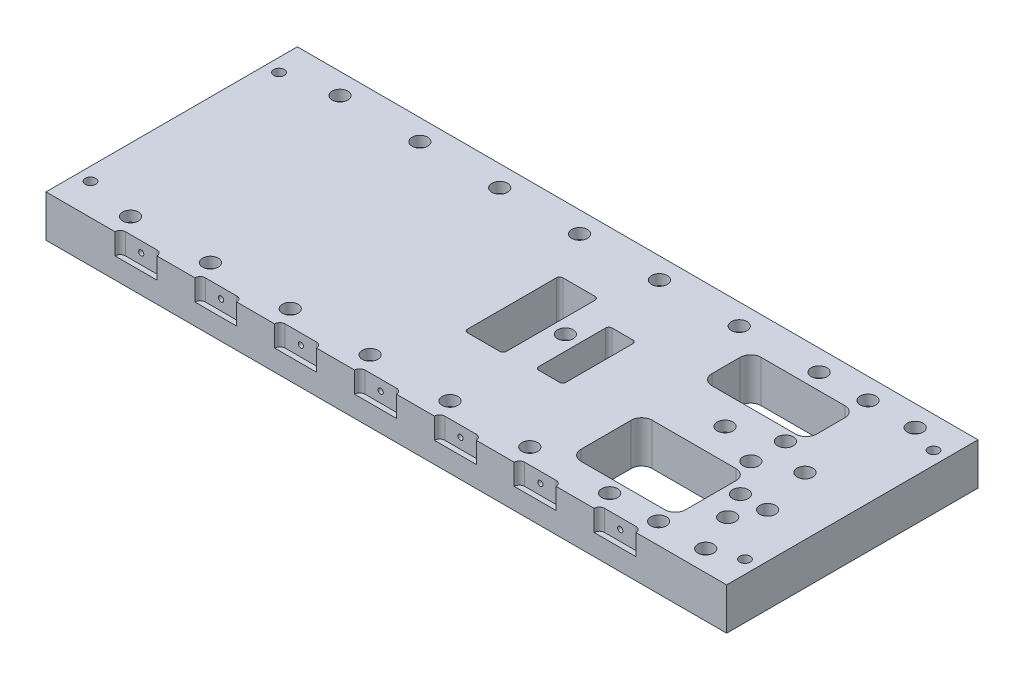
SolidWorks part; units mm, degrees
material "K110"
ref_plane "Front Plane" through (0, 0, 0) normal (0, 0, 1) x (1, 0, 0)
ref_plane "Top Plane" through (0, 0, 0) normal (0, 1, 0) x (1, 0, 0)
ref_plane "Right Plane" through (0, 0, 0) normal (1, 0, 0) x (0, 0, -1)
sketch "Sketch1" plane through (0, 0, 0) normal (0, 1, 0) x (1, 0, 0)
  line L1 (-325, -120) -> (325, -120)
  line L2 (-325, -120) -> (-325, 120)
  line L3 (-325, 120) -> (325, 120)
  line L4 (325, -120) -> (325, 120)
  line L5 (-325, -120) -> (325, 120) construction
  line L6 (-325, 120) -> (325, -120) construction
  point P0 (0, 0)
  dimension "D1" = 240
  dimension "D2" = 650
extrude "Boss-Extrude1" add sketch "Sketch1" against normal blind 40
sketch "Sketch2" plane through (0, 0, 0) normal (0, 1, 0) x (1, 0, 0)
  line L0 (187.25, -63.53) -> (187.25, -47.4) construction
  line L1 (184.25, -44.4) -> (180.25, -44.4) construction
  line L2 (174.25, -38.4) -> (174.25, -32.27) construction
  line L3 (174.25, -32.27) -> (172.25, -32.27) construction
  line L12 (169.25, -35.27) -> (169.25, -71.53) construction
  line L13 (172.25, -74.53) -> (214.25, -74.53) construction
  line L14 (199.25, -47.4) -> (199.25, -63.53) construction
  line L15 (206.25, -44.4) -> (202.25, -44.4) construction
  line L16 (212.25, -32.27) -> (212.25, -38.4) construction
  line L17 (214.25, -32.27) -> (212.25, -32.27) construction
  line L18 (217.25, -71.53) -> (217.25, -35.27) construction
  line L19 (187.25, -63.53) -> (187.25, -47.4)
  line L20 (184.25, -44.4) -> (180.25, -44.4)
  line L21 (174.25, -38.4) -> (174.25, -32.27)
  line L22 (174.25, -32.27) -> (172.25, -32.27)
  line L23 (169.25, -35.27) -> (169.25, -71.53)
  line L24 (172.25, -74.53) -> (214.25, -74.53)
  line L25 (199.25, -47.4) -> (199.25, -63.53)
  line L26 (206.25, -44.4) -> (202.25, -44.4)
  line L27 (212.25, -32.27) -> (212.25, -38.4)
  line L28 (214.25, -32.27) -> (212.25, -32.27)
  line L29 (217.25, -71.53) -> (217.25, -35.27)
  line L30 (212.25, 47.73) -> (214.25, 47.73) construction
  line L31 (212.25, 69.53) -> (212.25, 47.73) construction
  line L32 (174.25, 69.53) -> (212.25, 69.53) construction
  line L33 (174.25, 47.73) -> (174.25, 69.53) construction
  line L34 (172.25, 47.73) -> (174.25, 47.73) construction
  line L35 (169.25, 71.53) -> (169.25, 50.73) construction
  line L36 (214.25, 74.53) -> (172.25, 74.53) construction
  line L37 (217.25, 50.73) -> (217.25, 71.53) construction
  line L38 (212.25, 47.73) -> (214.25, 47.73)
  line L39 (212.25, 69.53) -> (212.25, 47.73)
  line L40 (174.25, 69.53) -> (212.25, 69.53)
  line L41 (174.25, 47.73) -> (174.25, 69.53)
  line L42 (172.25, 47.73) -> (174.25, 47.73)
  line L43 (169.25, 71.53) -> (169.25, 50.73)
  line L44 (214.25, 74.53) -> (172.25, 74.53)
  line L45 (217.25, 50.73) -> (217.25, 71.53)
  arc A0 (187.25, -47.4) -> (184.25, -44.4) centre (184.25, -47.4) ccw construction
  arc A1 (174.25, -38.4) -> (180.25, -44.4) centre (180.25, -38.4) ccw construction
  arc A2 (172.25, -32.27) -> (169.25, -35.27) centre (172.25, -35.27) ccw construction
  arc A3 (169.25, -71.53) -> (172.25, -74.53) centre (172.25, -71.53) ccw construction
  arc A4 (214.25, -74.53) -> (217.25, -71.53) centre (214.25, -71.53) ccw construction
  arc A5 (187.25, -63.53) -> (199.25, -63.53) centre (193.25, -63.53) ccw construction
  arc A6 (202.25, -44.4) -> (199.25, -47.4) centre (202.25, -47.4) ccw construction
  arc A7 (206.25, -44.4) -> (212.25, -38.4) centre (206.25, -38.4) ccw construction
  arc A8 (217.25, -35.27) -> (214.25, -32.27) centre (214.25, -35.27) ccw construction
  arc A9 (187.25, -47.4) -> (184.25, -44.4) centre (184.25, -47.4) ccw
  arc A10 (174.25, -38.4) -> (180.25, -44.4) centre (180.25, -38.4) ccw
  arc A11 (172.25, -32.27) -> (169.25, -35.27) centre (172.25, -35.27) ccw
  arc A12 (169.25, -71.53) -> (172.25, -74.53) centre (172.25, -71.53) ccw
  arc A13 (214.25, -74.53) -> (217.25, -71.53) centre (214.25, -71.53) ccw
  arc A14 (187.25, -63.53) -> (199.25, -63.53) centre (193.25, -63.53) ccw
  arc A15 (202.25, -44.4) -> (199.25, -47.4) centre (202.25, -47.4) ccw
  arc A16 (206.25, -44.4) -> (212.25, -38.4) centre (206.25, -38.4) ccw
  arc A17 (217.25, -35.27) -> (214.25, -32.27) centre (214.25, -35.27) ccw
  circle A18 centre (269.5, -63.53) radius 2.5 construction
  circle A19 centre (282.5, -38.4) radius 2.5 construction
  circle A20 centre (256.5, -38.4) radius 2.5 construction
  circle A21 centre (234.38, -6.27) radius 2.5 construction
  circle A22 centre (234.38, 26.73) radius 2.5 construction
  arc A23 (214.25, 47.73) -> (217.25, 50.73) centre (214.25, 50.73) ccw construction
  arc A24 (169.25, 50.73) -> (172.25, 47.73) centre (172.25, 50.73) ccw construction
  arc A25 (172.25, 74.53) -> (169.25, 71.53) centre (172.25, 71.53) ccw construction
  arc A26 (217.25, 71.53) -> (214.25, 74.53) centre (214.25, 71.53) ccw construction
  circle A27 centre (269.5, -63.53) radius 2.5
  circle A28 centre (282.5, -38.4) radius 2.5
  circle A29 centre (256.5, -38.4) radius 2.5
  circle A30 centre (234.38, -6.27) radius 2.5
  circle A31 centre (234.38, 26.73) radius 2.5
  arc A32 (214.25, 47.73) -> (217.25, 50.73) centre (214.25, 50.73) ccw
  arc A33 (169.25, 50.73) -> (172.25, 47.73) centre (172.25, 50.73) ccw
  arc A34 (172.25, 74.53) -> (169.25, 71.53) centre (172.25, 71.53) ccw
  arc A35 (217.25, 71.53) -> (214.25, 74.53) centre (214.25, 71.53) ccw
sketch "Sketch3" plane through (0, 0, 0) normal (0, 1, 0) x (1, 0, 0)
  line L1 (153.25, 84.63) -> (233.25, 84.63)
  line L2 (143.25, 74.63) -> (143.25, 47.63)
  line L3 (153.25, 37.63) -> (233.25, 37.63)
  line L4 (243.25, 74.63) -> (243.25, 47.63)
  line L8 (169.25, -53.4) -> (217.25, -53.4) construction
  line L9 (153.25, -19.4) -> (233.25, -19.4)
  line L10 (143.25, -29.4) -> (143.25, -77.4)
  line L11 (153.25, -87.4) -> (233.25, -87.4)
  line L12 (243.25, -29.4) -> (243.25, -77.4)
  line L13 (169.25, -35.27) -> (169.25, -71.53) construction
  line L14 (217.25, -71.53) -> (217.25, -35.27) construction
  line L15 (193.25, -74.53) -> (193.25, -19.4) construction
  line L16 (172.25, -74.53) -> (214.25, -74.53) construction
  line L17 (193.25, 84.63) -> (193.25, 47.73) construction
  line L18 (169.25, 61.13) -> (217.25, 61.13) construction
  line L19 (169.25, 71.53) -> (169.25, 50.73) construction
  line L20 (217.25, 50.73) -> (217.25, 71.53) construction
  arc A0 (143.25, 47.63) -> (153.25, 37.63) centre (153.25, 47.63) ccw
  arc A1 (233.25, 37.63) -> (243.25, 47.63) centre (233.25, 47.63) ccw
  arc A2 (243.25, 74.63) -> (233.25, 84.63) centre (233.25, 74.63) ccw
  arc A3 (153.25, 84.63) -> (143.25, 74.63) centre (153.25, 74.63) ccw
  circle A4 centre (234.38, 26.73) radius 7.5
  circle A5 centre (234.38, -6.27) radius 7.5
  circle A6 centre (269.5, -63.53) radius 7.5
  circle A7 centre (282.5, -38.4) radius 7.5
  circle A8 centre (256.5, -38.4) radius 7.5
  arc A9 (143.25, -77.4) -> (153.25, -87.4) centre (153.25, -77.4) ccw
  arc A10 (233.25, -87.4) -> (243.25, -77.4) centre (233.25, -77.4) ccw
  arc A11 (243.25, -29.4) -> (233.25, -19.4) centre (233.25, -29.4) ccw
  arc A12 (153.25, -19.4) -> (143.25, -29.4) centre (153.25, -29.4) ccw
  dimension "D5" = 10
  dimension "D6" = 15
  dimension "D11" = 10
  dimension "D2" = 100
  dimension "D3" = 47
  dimension "D7" = 68
  dimension "D8" = 100
extrude "Cut-Extrude2" cut sketch "Sketch3" against normal up to next
sketch "Sketch4" plane through (0, -40, 0) normal (0, -1, 0) x (1, 0, 0)
  circle A0 centre (234.38, -26.73) radius 9
  circle A1 centre (234.38, 6.27) radius 9
  circle A2 centre (256.5, 38.4) radius 9
  circle A3 centre (282.5, 38.4) radius 9
  circle A4 centre (269.5, 63.53) radius 9
  dimension "D1" = 18
extrude "Cut-Extrude3" cut sketch "Sketch4" against normal blind 5
extrude "Cut-Extrude9" cut sketch "Sketch11" against normal through all
sketch "Sketch11" plane through (304.63, 0, 0) normal (0, 1, 0) x (1, 0, 0)
  circle A0 centre (-35.13, 10.23) radius 7.5
  circle A1 centre (-111.38, 10.23) radius 7.5
  circle A2 centre (-263.88, 10.23) radius 7.5
extrude "Cut-Extrude10" cut sketch "Sketch12" against normal blind 5
sketch "Sketch12" plane through (304.63, -40, 0) normal (0, -1, 0) x (1, 0, 0)
  circle A0 centre (-35.13, -10.23) radius 10
extrude "Cut-Extrude11" cut sketch "Sketch13" against normal blind 30
sketch "Sketch13" plane through (304.63, -40, 0) normal (0, -1, 0) x (1, 0, 0)
  circle A0 centre (-111.38, -10.23) radius 10
  circle A4 centre (-263.88, -10.23) radius 7.5 construction
  circle A5 centre (-263.88, -10.23) radius 10
hole_wizard "M10 Tapped Hole1" positions "Sketch27" profile "Sketch15" tap size "M10" standard "ISO"
sketch "Sketch27" plane through (0, -40, 0) normal (0, -1, 0) x (-1, 0, 0)
  line L0 (-325, -120) -> (-325, 120) construction
  line L1 (-325, 120) -> (325, 120) construction
  line L2 (325, 120) -> (325, -120) construction
  line L3 (325, -120) -> (-325, -120) construction
  point P0 (-312.5, 107.5)
  point P2 (312.5, 107.5)
  point P4 (312.5, -107.5)
  point P6 (-312.5, -107.5)
  dimension "D1" = 12.5
  dimension "D2" = 12.5
  dimension "D3" = 12.5
  dimension "D4" = 12.5
sketch "Sketch15" plane through (312.5, -40, -107.5) normal (1, 0, 0) x (0, 0, -1)
  line L0 (0, 0) -> (0, 30.0537)
  line L1 (0, 30.0537) -> (4.25, 27.5)
  line L2 (4.25, 27.5) -> (4.25, 0.775)
  line L3 (4.25, 0.775) -> (5.025, 0)
  line L5 (5.025, 0) -> (0, 0)
  line L6 (-4.25, 0.775) -> (-5.025, 0) construction
  line L10 (0, 30.0537) -> (-4.25, 27.5) construction
  line L11 (0, -6.35) -> (0, 107.95) construction
  dimension "Tap Drill Dia." = 8.5
  dimension "Tap Drill Depth" = 27.5
  dimension "Near C'Sink Dia." = 10.05
  dimension "Near C'Sink Angle" = 90
  dimension "Drill Angle" = 118
cosmetic thread "Hole Thread1" parameters "D1"=20, "D2"=10
cosmetic thread "Hole Thread2" parameters "D1"=20, "D2"=10
cosmetic thread "Hole Thread3" parameters "D1"=20, "D2"=10
cosmetic thread "Hole Thread4" parameters "D1"=20, "D2"=10
hole_wizard "Ø10.0mm Dowel Hole2" positions "Sketch26" profile "Sketch25" hole size "Ø10.0" standard "ISO" end condition through all
sketch "Sketch26" plane through (0, -40, 0) normal (0, -1, 0) x (-1, 0, 0)
  line L0 (-325, -120) -> (-325, 120) construction
  line L1 (325, 120) -> (325, -120) construction
  circle A0 centre (-312.5, 107.5) radius 4.25 construction
  circle A1 centre (-312.5, -107.5) radius 4.25 construction
  point P0 (-312.5, 90)
  point P2 (312.5, 90)
  point P4 (312.5, -90)
  point P6 (-312.5, -90)
  dimension "D4" = 17.5
  dimension "D1" = 12.5
  dimension "D2" = 17.5
  dimension "D3" = 12.5
sketch "Sketch25" plane through (312.5, -40, -90) normal (1, 0, 0) x (0, 0, -1)
  line L0 (0, 0) -> (0, 40)
  line L1 (0, 40) -> (5, 40)
  line L2 (5, 40) -> (5, 0)
  line L5 (5, 0) -> (0, 0)
  line L11 (0, -6.35) -> (0, 107.95) construction
  dimension "Thru Hole Dia." = 10
  dimension "Thru Hole Depth" = 40
sketch "Sketch28" plane through (0, 0, 0) normal (0, 1, 0) x (1, 0, 0)
  line L0 (-315.37, -95) -> (304.63, -95) construction
  line L2 (325, -120) -> (325, 120) construction
  circle A0 centre (240, -100) radius 7.5
  circle A1 centre (285, -100) radius 7.5
  circle A2 centre (117, -100) radius 7.5
  circle A3 centre (40.75, -100) radius 7.5
  circle A4 centre (193.25, -100) radius 7.5
  circle A5 centre (-35.5, -100) radius 7.5
  circle A6 centre (-111.75, -100) radius 7.5
  circle A7 centre (-188, -100) radius 7.5
  circle A8 centre (-264.25, -100) radius 7.5
  dimension "D1" = 15
  dimension "D2" = 5
  dimension "D3" = 46.75
  dimension "D4" = 40
  dimension "D5" = 45
  dimension "D7" = 76.25
  dimension "D6" = 7
extrude "Cut-Extrude12" cut sketch "Sketch28" against normal up to next
mirror "Mirror1" about plane through (0, 0, 0) normal (0, 0, 1) of "Cut-Extrude12"
sketch "Sketch29" plane through (0, -40, 0) normal (0, -1, 0) x (1, 0, 0)
  circle A0 centre (193.25, 100) radius 9
  circle A1 centre (240, 100) radius 9
  circle A2 centre (240, -100) radius 9
  circle A3 centre (193.25, -100) radius 9
  circle A4 centre (285, 100) radius 9
  circle A5 centre (285, -100) radius 9
  circle A6 centre (117, 100) radius 9
  circle A7 centre (117, -100) radius 9
  circle A8 centre (40.75, 100) radius 9
  circle A9 centre (40.75, -100) radius 9
  circle A10 centre (-35.5, 100) radius 9
  circle A11 centre (-35.5, -100) radius 9
  circle A12 centre (-111.75, 100) radius 9
  circle A13 centre (-111.75, -100) radius 9
  circle A14 centre (-188, 100) radius 9
  circle A15 centre (-188, -100) radius 9
  circle A16 centre (-264.25, 100) radius 9
  circle A17 centre (-264.25, -100) radius 9
  dimension "D1" = 18
  dimension "D2" = 7
extrude "Cut-Extrude13" cut sketch "Sketch29" against normal blind 30
extrude "Cut-Extrude14" cut sketch "Sketch30" against normal blind 20
sketch "Sketch30" plane through (304.63, 0, 0) normal (0, 1, 0) x (1, 0, 0)
  line L1 (-106.25, -120) -> (-66.25, -120)
  line L3 (-101.25, -115) -> (-71.25, -115)
  arc A0 (-106.25, -120) -> (-101.25, -115) centre (-101.25, -120) cw
  arc A1 (-66.25, -120) -> (-71.25, -115) centre (-71.25, -120) ccw
hole_wizard "M6 Tapped Hole1" positions "Sketch37" profile "Sketch32" tap size "M6" standard "ISO"
sketch "Sketch37" plane through (0, 0, 115) normal (0, 0, 1) x (1, 0, 0)
  line L4 (218.38, -20) -> (218.38, 0) construction
  line L5 (198.38, -20) -> (238.38, -20) construction
  line L6 (233.38, 0) -> (203.38, 0) construction
  line L7 (132, 0) -> (-132, 0) construction
  point P2 (218.38, -10)
  dimension "D1" = 10
sketch "Sketch32" plane through (218.38, -10, 115) normal (1, 0, 0) x (0, -1, 0)
  line L0 (0, 0) -> (0, 11.5022)
  line L1 (0, 11.5022) -> (2.5, 10)
  line L2 (2.5, 10) -> (2.5, 0)
  line L5 (2.5, 0) -> (0, 0)
  line L10 (0, 11.5022) -> (-2.5, 10) construction
  line L11 (0, -6.35) -> (0, 107.95) construction
  dimension "Tap Drill Dia." = 5
  dimension "Tap Drill Depth" = 10
  dimension "Drill Angle" = 118
cosmetic thread "Hole Thread5" parameters "D1"=8, "D2"=6
pattern_linear "LPattern1" count 7 spacing 76.25 along (-1, 0, 0) of "M6 Tapped Hole1", "Cut-Extrude14"
cosmetic thread "Hole Thread6" parameters "D1"=8, "D2"=6
cosmetic thread "Hole Thread7" parameters "D1"=8, "D2"=6
cosmetic thread "Hole Thread8" parameters "D1"=8, "D2"=6
cosmetic thread "Hole Thread9" parameters "D1"=8, "D2"=6
cosmetic thread "Hole Thread10" parameters "D1"=8, "D2"=6
cosmetic thread "Hole Thread11" parameters "D1"=8, "D2"=6
sketch "Sketch38" plane through (0, 0, 0) normal (0, 1, 0) x (1, 0, 0)
  line L0 (75.88, -10.27) -> (75.88, 15.73) construction
  line L1 (57.75, -32.27) -> (77.75, -32.27)
  line L2 (54.75, -29.27) -> (54.75, 34.73)
  line L3 (57.75, 37.73) -> (77.75, 37.73)
  line L4 (80.75, -29.27) -> (80.75, 34.73)
  line L5 (72.88, 18.73) -> (59.75, 18.73) construction
  line L6 (59.75, -11.27) -> (59.75, -13.27) construction
  line L7 (59.75, -13.27) -> (72.88, -13.27) construction
  arc A1 (57.75, -32.27) -> (54.75, -29.27) centre (57.75, -29.27) cw
  arc A2 (77.75, -32.27) -> (80.75, -29.27) centre (77.75, -29.27) ccw
  arc A3 (77.75, 37.73) -> (80.75, 34.73) centre (77.75, 34.73) cw
  arc A4 (54.75, 34.73) -> (57.75, 37.73) centre (57.75, 34.73) cw
  point P18 (80.75, 37.73)
  point P21 (54.75, 37.73)
  dimension "D7" = 3
  dimension "D1" = 4.87
  dimension "D2" = 19
  dimension "D3" = 5
  dimension "D4" = 19
  dimension "D5" = 70
  dimension "D6" = 26
extrude "Cut-Extrude15" cut sketch "Sketch38" against normal up to next
sketch "Sketch39" plane through (0, 0, 0) normal (0, 1, 0) x (1, 0, 0)
  line L0 (-5.37, 11.73) -> (-5.37, -6.27) construction
  line L1 (-7.25, -35.27) -> (23.75, -35.27)
  line L2 (-10.25, -32.27) -> (-10.25, 52.73)
  line L3 (-7.25, 55.73) -> (23.75, 55.73)
  line L4 (26.75, -32.27) -> (26.75, 52.73)
  line L5 (21.75, -17.27) -> (21.75, -13.77) construction
  line L6 (-2.37, -17.27) -> (21.75, -17.27) construction
  line L7 (21.75, 37.73) -> (-2.37, 37.73) construction
  arc A0 (23.75, 55.73) -> (26.75, 52.73) centre (23.75, 52.73) cw
  arc A1 (-10.25, 52.73) -> (-7.25, 55.73) centre (-7.25, 52.73) cw
  arc A2 (-7.25, -35.27) -> (-10.25, -32.27) centre (-7.25, -32.27) cw
  arc A3 (23.75, -35.27) -> (26.75, -32.27) centre (23.75, -32.27) ccw
  point P14 (26.75, 55.73)
  point P17 (-10.25, 55.73)
  point P22 (26.75, -35.27)
  dimension "D7" = 3
  dimension "D1" = 4.88
  dimension "D2" = 5
  dimension "D3" = 18
  dimension "D4" = 18
  dimension "D5" = 91
  dimension "D6" = 37
extrude "Cut-Extrude16" cut sketch "Sketch39" against normal up to next
